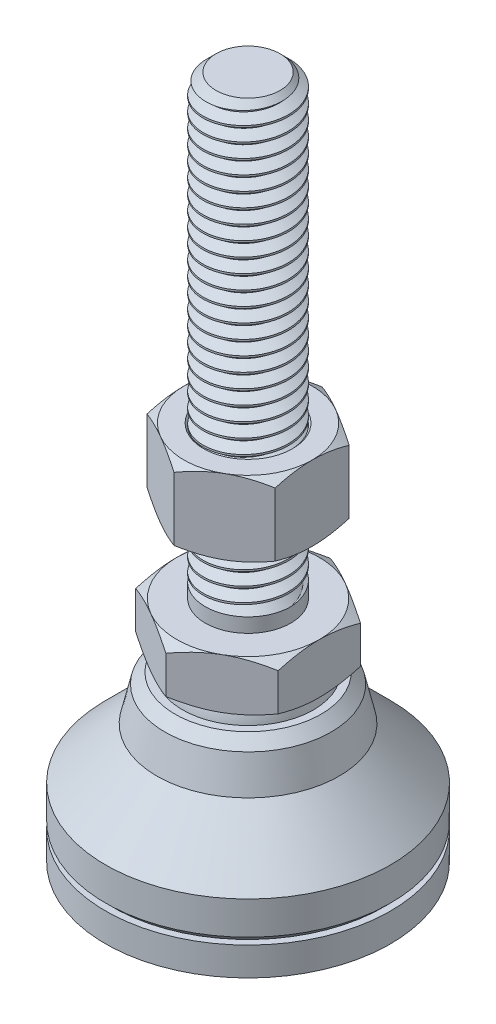
SolidWorks part; units mm, degrees
ref_plane "Front Plane" through (0, 0, 0) normal (0, 0, 1) x (1, 0, 0)
ref_plane "Top Plane" through (0, 0, 0) normal (0, 1, 0) x (1, 0, 0)
ref_plane "Right Plane" through (0, 0, 0) normal (1, 0, 0) x (0, 0, -1)
sketch "Sketch1" plane through (0, 0, 0) normal (0, 0, 1) x (1, 0, 0)
  line L0 (0, 0) -> (0, 76.2) construction
  line L1 (-15.875, 0) -> (15.875, 0) construction
  line L2 (-4.7625, 76.2) -> (4.7625, 76.2) construction
  line L3 (-7.9375, 19.812) -> (7.9375, 19.812) construction
  point P7 (0, 25.4)
  point P10 (0, 19.812)
  point P11 (-7.9375, 25.4)
  point P12 (0, 3.175)
  dimension "D1" = 3.175
sketch "Sketch2" plane through (0, 0, 0) normal (0, 0, 1) x (1, 0, 0)
  line L0 (0, 3.175) -> (0, 9.7663)
  line L1 (-7.3787, 19.812) -> (-7.9375, 19.812) construction
  line L2 (-9.271, 17.145) -> (-8.128, 18.288)
  line L3 (-8.128, 18.288) -> (-7.2896, 18.288)
  line L4 (-9.271, 17.145) -> (-10.16, 13.335)
  line L5 (-10.16, 13.335) -> (-15.875, 7.62)
  line L6 (-15.875, 7.62) -> (-15.875, 3.937)
  line L7 (-15.113, 3.175) -> (0, 3.175)
  line L8 (-9.271, 17.145) -> (0, 17.145) construction
  line L9 (-7.3787, 17.145) -> (-7.3787, 19.812) construction
  line L10 (-15.875, 3.937) -> (-15.113, 3.175)
  line L11 (-15.113, 3.175) -> (-15.875, 3.175) construction
  line L12 (-15.875, 3.175) -> (-15.875, 3.937) construction
  line L13 (0, 19.812) -> (0, 76.2) construction
  line L14 (-4.7625, 76.2) -> (4.7625, 76.2) construction
  line L15 (-7.9375, 19.812) -> (7.9375, 19.812) construction
  circle A0 centre (0, 17.145) radius 7.3787 construction
  arc A2 (-7.2896, 18.288) -> (0, 9.7663) centre (0, 17.145) ccw
  dimension "D1" = 20.32
  dimension "D2" = 18.542
  dimension "D3" = 16.256
  dimension "D4" = 0.5588
  dimension "H3" = 3.81
  dimension "C1" = 0.762
  dimension "H4" = 1.143
  dimension "H2" = 5.715
  dimension "H1" = 4.445
revolve "Revolve1" add sketch "Sketch2" angle 360 about L0
sketch "Sketch12" plane through (0, 0, 0) normal (0, 0, 1) x (1, 0, 0)
  line L0 (0, 19.812) -> (-6.8798, 19.812)
  line L1 (0, 19.812) -> (0, 9.7663)
  arc A0 (-6.8798, 19.812) -> (0, 9.7663) centre (0, 17.145) ccw
  circle A1 centre (0, 17.145) radius 7.3787 construction
revolve "Revolve2" add sketch "Sketch12" angle 360 about L1
sketch "Sketch4" plane through (0, 19.812, 0) normal (0, 1, 0) x (1, 0, 0)
  line L1 (0, 9.1654) -> (-7.9375, 4.5827)
  line L2 (-7.9375, 4.5827) -> (-7.9375, -4.5827)
  line L3 (-7.9375, -4.5827) -> (0, -9.1654)
  line L4 (0, -9.1654) -> (7.9375, -4.5827)
  line L5 (7.9375, -4.5827) -> (7.9375, 4.5827)
  line L6 (7.9375, 4.5827) -> (0, 9.1654)
  circle A0 centre (0, 0) radius 7.9375 construction
extrude "Boss-Extrude1" add sketch "Sketch4" along normal up to vertex (5.588 mm away) up to point (0, 25.4, 0)
sketch "Sketch5" plane through (0, 0, 0) normal (1, 0, 0) x (0, 0, -1)
  line L0 (-10.3934, 25.4) -> (-10.3934, 19.812)
  line L1 (-10.3934, 19.812) -> (-7.9375, 19.812)
  line L2 (-7.9375, 19.812) -> (-9.1654, 20.5209)
  line L3 (-9.1654, 20.5209) -> (-9.1654, 24.6911)
  line L4 (-9.1654, 24.6911) -> (-7.9375, 25.4)
  line L5 (-7.9375, 25.4) -> (-10.3934, 25.4)
  line L9 (-9.1654, 25.4) -> (-9.1654, 19.812) construction
  dimension "D1" = 30
revolve "Cut-Revolve2" cut sketch "Sketch5" angle 360 about L0
sketch "Sketch6" plane through (0, 25.4, 0) normal (0, 1, 0) x (1, 0, 0)
  circle A0 centre (0, 0) radius 4.7625
extrude "Boss-Extrude2" add sketch "Sketch6" along normal up to vertex (50.8 mm away) separate body up to point (0, 76.2, 0)
sketch "Sketch7" plane through (0, 76.2, 0) normal (0, 1, 0) x (1, 0, 0)
  circle A1 centre (0, 0) radius 4.7625
  circle A2 centre (0, 0) radius 4.7625
  point P0 (4.7625, 0)
  dimension "D1" = 0
curve "Helix/Spiral1" pitch 1.5875 height 52.3875 turns 33 parameters "Pitch"=1.5875
sketch "Sketch8" plane through (0, 0, 0) normal (0, 0, 1) x (1, 0, 0)
  line L0 (4.9344, 77.6883) -> (4.9344, 76.1008) construction
  line L1 (4.9344, 76.1008) -> (3.5595, 76.8945) construction
  line L2 (3.5595, 76.8945) -> (4.9344, 77.6883) construction
  line L3 (3.7314, 76.9938) -> (3.7314, 76.7953) construction
  line L4 (4.7625, 77.5891) -> (4.7625, 76.2) construction
  line L5 (3.5595, 76.8945) -> (3.7314, 76.8945) construction
  line L6 (4.7625, 76.8945) -> (4.9344, 76.8945) construction
  line L7 (4.8484, 77.6387) -> (3.7314, 76.9938)
  line L8 (3.7314, 76.9938) -> (3.7314, 76.7953)
  line L9 (3.7314, 76.7953) -> (4.8484, 76.1504)
  line L10 (4.8484, 76.1504) -> (4.8484, 77.6387)
  line L11 (4.9344, 76.1008) -> (4.7625, 76.1008) construction
  line L12 (4.7625, 76.1008) -> (4.7625, 50.7008) construction
  line L20 (4.7625, 25.4) -> (4.7625, 76.2) construction
  point P11 (4.8484, 76.8945)
  dimension "D1" = 1.5875
  dimension "D2" = 0.1984
  dimension "D3" = 25.4
sketch "Sketch9" plane through (0, 76.2, 0) normal (0, 1, 0) x (1, 0, 0)
  circle A0 centre (0, 0) radius 3.5595
sweep "Cut-Sweep1" cut profiles "Sketch8" path "Helix/Spiral1"
extrude "Cut-Extrude1" cut sketch "Sketch9" against normal up to vertex (50.8 mm away) draft 45 flip side to cut up to point (0, 25.4, 0)
combine bodies "Combine1" operation type add bodies to combine 107 104
ref_plane "Plane1" through (0, 42.3333, 0) normal (0, 1, 0) x (-1, 0, 0)
sketch "Sketch10" plane through (0, 42.3333, 0) normal (0, 1, 0) x (-1, 0, 0)
  line L1 (0, 8.2489) -> (-7.1438, 4.1244)
  line L2 (-7.1438, 4.1244) -> (-7.1438, -4.1244)
  line L3 (-7.1438, -4.1244) -> (0, -8.2489)
  line L4 (0, -8.2489) -> (7.1437, -4.1244)
  line L5 (7.1437, -4.1244) -> (7.1437, 4.1244)
  line L6 (7.1437, 4.1244) -> (0, 8.2489)
  circle A0 centre (0, 0) radius 7.1438 construction
  circle A1 centre (0, 0) radius 4.7625
  dimension "Nut Width" = 14.2875
extrude "Boss-Extrude3" add sketch "Sketch10" against normal blind 8.3344 separate body
sketch "Sketch11" plane through (0, 0, 0) normal (1, 0, 0) x (0, 0, -1)
  line L0 (-9.354, 33.999) -> (-9.354, 42.3333)
  line L1 (-9.354, 42.3333) -> (-7.1438, 42.3333)
  line L2 (-7.1438, 42.3333) -> (-8.2489, 41.6953)
  line L3 (-8.2489, 41.6953) -> (-8.2489, 34.637)
  line L4 (-8.2489, 34.637) -> (-7.1438, 33.999)
  line L5 (-7.1438, 33.999) -> (-9.354, 33.999)
  line L6 (-8.2489, 33.999) -> (-8.2489, 42.3333) construction
  line L11 (0, 33.999) -> (0, 42.3333)
  line L12 (0, 42.3333) -> (4.9609, 42.3333)
  line L13 (4.9609, 42.3333) -> (4.7625, 42.1349)
  line L14 (4.7625, 42.1349) -> (4.7625, 34.1974)
  line L15 (4.7625, 34.1974) -> (4.9609, 33.999)
  line L16 (4.9609, 33.999) -> (0, 33.999)
  line L17 (4.7625, 33.999) -> (4.7625, 42.3333) construction
  line L19 (0, 0) -> (0, 76.2) construction
  dimension "D2" = 45
  dimension "D3" = 0.1984
  dimension "D1" = 60
revolve "Cut-Revolve3" cut sketch "Sketch11" angle 360 about L0
sketch "Sketch13" plane through (0, 0, 0) normal (0, 0, 1) x (1, 0, 0)
  line L0 (0, 0) -> (0, 76.2) construction
  line L1 (0, 31.75) -> (4.7625, 26.9875)
  line L2 (0, 31.75) -> (0, 25.4)
  line L3 (0, 25.4) -> (4.7625, 25.4)
  line L4 (4.7625, 26.9875) -> (4.7625, 25.4)
  dimension "D1" = 45
  dimension "D2" = 1.5875
revolve "Revolve3" add sketch "Sketch13" angle 360 about L2
sketch "SketchX" plane through (0, 0, 0) normal (0, 0, 1) x (1, 0, 0)
  line L0 (0, 17.145) -> (-7.7082, 75.6948)
  line L1 (0, 17.145) -> (7.7082, 75.6948)
  line L2 (0, 0) -> (0, 76.2) construction
  line L3 (0, 17.145) -> (0, 76.2)
  arc A0 (-7.7082, 75.6948) -> (7.7082, 75.6948) centre (0, 17.145) cw construction
  dimension "D1" = 7.5
sketch "Sketch14" plane through (0, 0, 0) normal (0, 0, 1) x (1, 0, 0)
  line L1 (0, 0) -> (15.875, 0)
  line L2 (0, 0) -> (0, 3.175)
  line L3 (0, 3.175) -> (15.875, 3.175)
  line L4 (15.875, 0) -> (15.875, 3.175)
  point P5 (15.875, 1.5875)
revolve "Revolve4" add sketch "Sketch14" angle 360 about L2
equation "\"D3@Helix/Spiral1\" = \"Pitch@Helix/Spiral1\" + \"Thread Lg.@Sketch1\""
equation "\"D1@Sketch8\" = \"Pitch@Helix/Spiral1\" "
equation "\"D2@Sketch8\" = \"D1@Sketch8\" / 8"
equation "\"D1@Plane1\" = \"Thread Lg.@Sketch1\" / 1.5"
equation "\"D3@Sketch11\" = \"Pitch@Helix/Spiral1\" / 8"
equation "\"D2@Sketch13\" = \"Pitch@Helix/Spiral1\""
equation "\"D3@Sketch8\" = \"Thread Lg.@Sketch1\" / 2"
